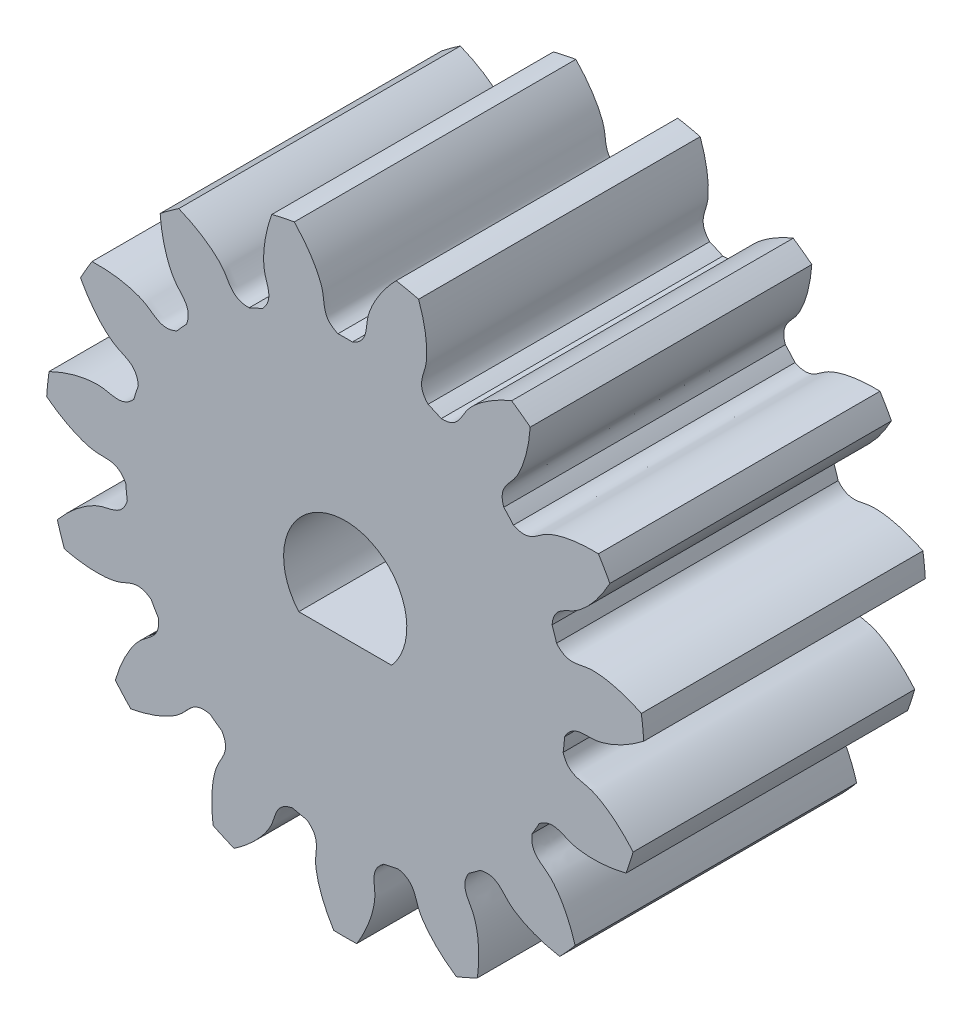
SolidWorks part; units mm, degrees
material "尼龙6"
ref_plane "前视基准面" through (0, 0, 0) normal (0, 0, 1) x (1, 0, 0)
ref_plane "上视基准面" through (0, 0, 0) normal (0, 1, 0) x (1, 0, 0)
ref_plane "右视基准面" through (0, 0, 0) normal (1, 0, 0) x (0, 0, -1)
sketch "草图1" plane through (0, 0, 0) normal (0, 0, 1) x (1, 0, 0)
  circle A0 centre (0, 0) radius 8.5
  dimension "D1" = 17
extrude "凸台-拉伸1" add sketch "草图1" along normal blind 8
ref_axis "基准轴1" through (0, 0, -1.5) along (0, 0, 1)
sketch "草图2" plane through (0, 0, 0) normal (0, 0, 1) x (1, 0, 0)
  line L0 (0, 0) -> (0, 8.5) construction
  circle A0 centre (0, 0) radius 8.5 construction
  arc A1 (0.2043, 6.2467) -> (-0.2043, 6.2467) centre (0, 0) ccw
  arc A2 (3.2468, 9.6359) -> (-3.2468, 9.6359) centre (0, 0) ccw
  spline S0 degree 3 poles (0.2043, 6.2467) (0.6572, 6.4344) (0.5721, 6.7863) (0.6513, 7.1085) (0.6574, 7.1317) (0.6648, 7.1574) (0.6736, 7.1857) (0.6838, 7.2164) (0.6956, 7.2497) (0.709, 7.2853) (0.7242, 7.3232) (0.7412, 7.3635) (0.7602, 7.4059) (0.7812, 7.4506) (0.8044, 7.4973) (0.8298, 7.5461) (0.8575, 7.5968) (0.8876, 7.6494) (0.9203, 7.7038) (0.9555, 7.7599) (0.9933, 7.8177) (1.0339, 7.877) (1.0774, 7.9378) (1.1237, 7.9999) (1.1729, 8.0634) (1.2253, 8.1281) (1.2807, 8.1938) (1.3392, 8.2606) (1.401, 8.3282) (1.4661, 8.3967) (1.5345, 8.4658) (1.6063, 8.5355) (1.6816, 8.6057) (1.7603, 8.6763) (1.8426, 8.7471) (1.9284, 8.818) (2.0178, 8.889) (2.1109, 8.9599) (2.2077, 9.0305) (2.3082, 9.1008) (2.4124, 9.1707) (2.5203, 9.24) (2.632, 9.3086) (2.7475, 9.3764) (2.8668, 9.4432) (3.0326, 9.5318) (3.1602, 9.595) (3.2468, 9.6359) knots 0 0 0 0 0.202473 0.206979 0.212085 0.217793 0.224101 0.23101 0.23852 0.24663 0.255341 0.264653 0.274566 0.285079 0.296194 0.307909 0.320225 0.333141 0.346659 0.360777 0.375496 0.390816 0.406736 0.423257 0.440379 0.458102 0.476426 0.49535 0.514875 0.535001 0.555728 0.577055 0.598984 0.621513 0.644642 0.668373 0.692704 0.717636 0.743169 0.769303 0.796037 0.823373 0.851309 0.879845 0.908983 0.938721 1 1 1 1
  spline S1 degree 3 poles (-0.2043, 6.2467) (-0.6572, 6.4344) (-0.5721, 6.7863) (-0.6513, 7.1085) (-0.6574, 7.1317) (-0.6648, 7.1574) (-0.6736, 7.1857) (-0.6838, 7.2164) (-0.6956, 7.2497) (-0.709, 7.2853) (-0.7242, 7.3232) (-0.7412, 7.3635) (-0.7602, 7.4059) (-0.7812, 7.4506) (-0.8044, 7.4973) (-0.8298, 7.5461) (-0.8575, 7.5968) (-0.8876, 7.6494) (-0.9203, 7.7038) (-0.9555, 7.7599) (-0.9933, 7.8177) (-1.0339, 7.877) (-1.0774, 7.9378) (-1.1237, 7.9999) (-1.1729, 8.0634) (-1.2253, 8.1281) (-1.2807, 8.1938) (-1.3392, 8.2606) (-1.401, 8.3282) (-1.4661, 8.3967) (-1.5345, 8.4658) (-1.6063, 8.5355) (-1.6816, 8.6057) (-1.7603, 8.6763) (-1.8426, 8.7471) (-1.9284, 8.818) (-2.0178, 8.889) (-2.1109, 8.9599) (-2.2077, 9.0305) (-2.3082, 9.1008) (-2.4124, 9.1707) (-2.5203, 9.24) (-2.632, 9.3086) (-2.7475, 9.3764) (-2.8668, 9.4432) (-3.0326, 9.5318) (-3.1602, 9.595) (-3.2468, 9.6359) knots 0 0 0 0 0.202473 0.206979 0.212085 0.217793 0.224101 0.23101 0.23852 0.24663 0.255341 0.264653 0.274566 0.285079 0.296194 0.307909 0.320225 0.333141 0.346659 0.360777 0.375496 0.390816 0.406736 0.423257 0.440379 0.458102 0.476426 0.49535 0.514875 0.535001 0.555728 0.577055 0.598984 0.621513 0.644642 0.668373 0.692704 0.717636 0.743169 0.769303 0.796037 0.823373 0.851309 0.879845 0.908983 0.938721 1 1 1 1
extrude "切除-拉伸1" cut sketch "草图2" along normal through all
pattern_circular "阵列(圆周)1" count 15 every 24 about axis through (0, 0, -1.5) along (0, 0, 1) of "切除-拉伸1"
sketch "草图3" plane through (0, 0, 0) normal (0, 0, 1) x (1, 0, 0)
  circle A0 centre (0, 0) radius 7.5 construction
  dimension "Dn" = 15
sketch "草图4" plane through (0, 0, 8) normal (0, 0, 1) x (1, 0, 0)
  line L1 (-1.3191, -1.15) -> (1.3191, -1.15)
  line L2 (0, 0) -> (0, 1.75) construction
  arc A1 (1.3191, -1.15) -> (-1.3191, -1.15) centre (0, 0) ccw
  dimension "D1" = 3.5
  dimension "D2" = 2.9
extrude "切除-拉伸2" cut sketch "草图4" against normal blind 6
